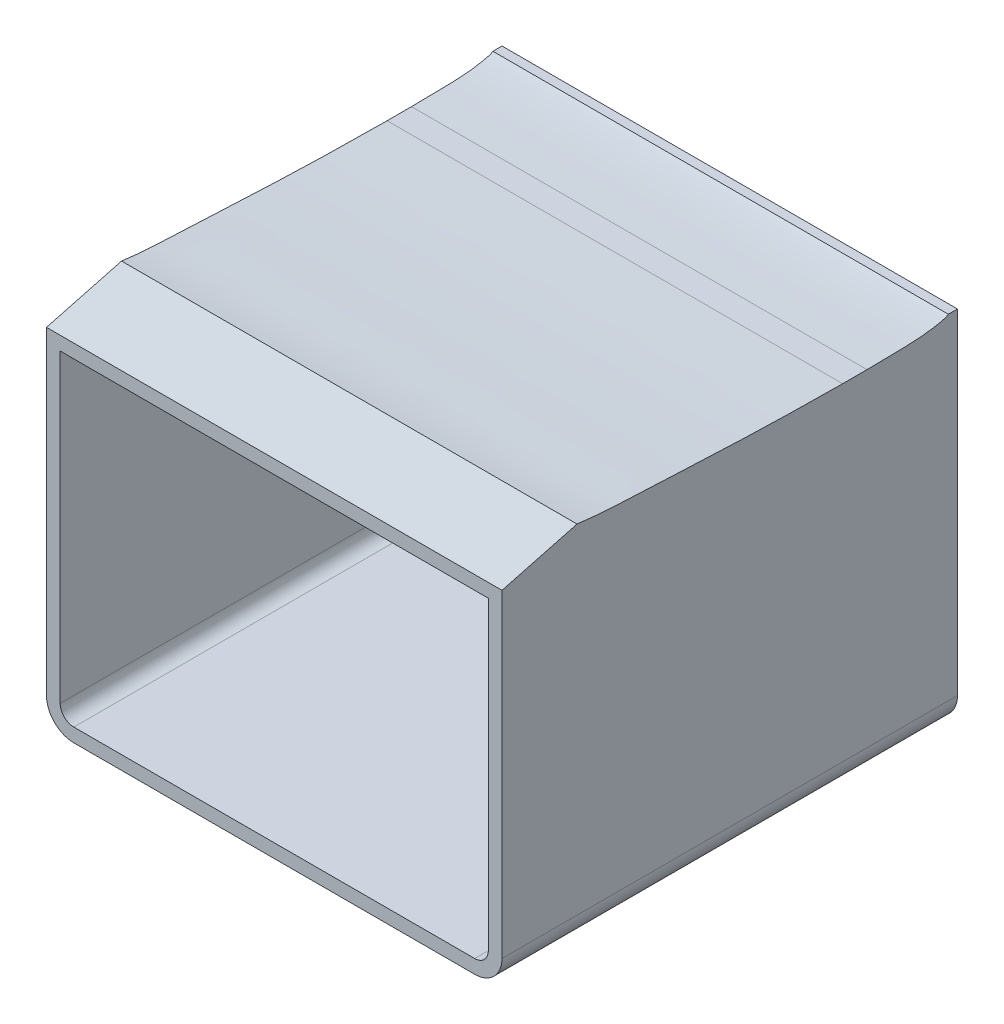
SolidWorks part; units mm, degrees
ref_plane "Front Plane" through (0, 0, 0) normal (0, 0, 1) x (1, 0, 0)
ref_plane "Top Plane" through (0, 0, 0) normal (0, 1, 0) x (1, 0, 0)
ref_plane "Right Plane" through (0, 0, 0) normal (1, 0, 0) x (0, 0, -1)
sketch "Sketch1" plane through (0, 0, 0) normal (0, 0, 1) x (1, 0, 0)
  line L1 (-44, -41) -> (44, -41)
  line L2 (-50, -35) -> (-50, 35)
  line L3 (-50, 35) -> (50, 35)
  line L4 (50, -35) -> (50, 35)
  line L5 (0, 35) -> (0, -41) construction
  line L6 (-50, 0) -> (50, 0) construction
  arc A0 (44, -41) -> (50, -35) centre (44, -35) ccw
  arc A1 (-44, -41) -> (-50, -35) centre (-44, -35) cw
  point P0 (0, 0)
  point P9 (-50, -41)
  dimension "D3" = 6
  dimension "D1" = 100
  dimension "D2" = 70
extrude "Boss-Extrude1" add sketch "Sketch1" along normal mid plane 100
shell "Shell1" thickness 3 removed face at (0, -14.0809, 50) removed face at (0, -14.0809, -50)
sketch "Sketch2" plane through (0, 0, 0) normal (1, 0, 0) x (0, 0, -1)
  line L0 (50, 35) -> (50, 48.6969) construction
  line L1 (50, 38.4921) -> (48, 38.4921) construction
  line L2 (24.7891, 36.8885) -> (30.129, 36.9004)
  line L5 (-50, 35) -> (50, 35)
  line L6 (48, 38.4921) -> (50, 38.4921)
  line L7 (50, 38.4921) -> (50, 35)
  line L8 (-33.5256, 39.3705) -> (-50, 35)
  spline S0 degree 3 poles (48, 38.4921) (47.8452, 38.3824) (47.6783, 38.2895) (47.335, 38.1365) (47.156, 38.0796) (46.7924, 37.9816) (46.6083, 37.9394) (46.2409, 37.8558) (46.0569, 37.8155) (45.1355, 37.6227) (44.3933, 37.4968) (42.8991, 37.3006) (42.1482, 37.2289) (40.6478, 37.1204) (39.8971, 37.083) (37.6442, 36.9966) (36.1412, 36.9757) (33.1353, 36.9326) (31.6322, 36.9133) (30.129, 36.9004) knots 0 0 0 0 0.03125 0.03125 0.0625 0.0625 0.09375 0.09375 0.125 0.125 0.25 0.25 0.375 0.375 0.5 0.5 0.75 0.75 1 1 1 1
  spline S1 degree 2 poles (-33.5256, 39.3705) (-31.4044, 39.0974) (-29.8953, 38.9547) (-28.2607, 38.8002) (-26.2565, 38.6844) (-24.8643, 38.604) (-22.612, 38.5077) (-21.7006, 38.4688) (-20.7892, 38.4303) (-20.0417, 38.3987) (-18.9666, 38.3482) (-17.4773, 38.2782) (-15.3224, 38.1672) (-13.5005, 38.0733) (-11.6786, 37.9787) (-8.4882, 37.813) (-4.389, 37.6374) (4.6129, 37.2516) (10.1962, 37.1163) (12.9629, 37.0493) (17.4921, 36.9814) (19.9717, 36.9442) (21.1404, 36.9276) (23.3305, 36.8964) (24.7891, 36.8885) knots 0 0 0 0.0625 0.0625 0.125 0.125 0.1875 0.1875 0.21875 0.21875 0.25 0.25 0.3125 0.3125 0.375 0.375 0.5 0.5 0.75 0.75 0.875 0.875 0.9375 0.9375 1 1 1
  dimension "D1" = 2
  dimension "D2" = 1.9004
  dimension "D5" = 5.34
extrude "Boss-Extrude2" add sketch "Sketch2" along normal mid plane 100
